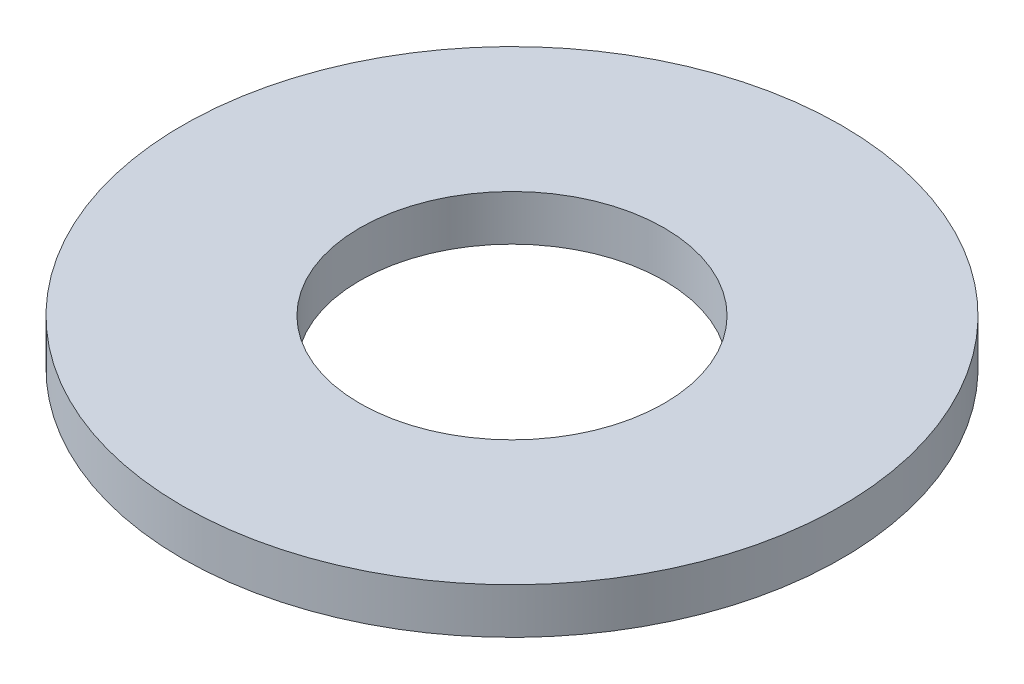
SolidWorks part; units mm, degrees
ref_plane "Front Plane" through (0, 0, 0) normal (0, 0, 1) x (1, 0, 0)
ref_plane "Top Plane" through (0, 0, 0) normal (0, 1, 0) x (1, 0, 0)
ref_plane "Right Plane" through (0, 0, 0) normal (1, 0, 0) x (0, 0, -1)
sketch "Sketch1" plane through (0, 0, 0) normal (0, 1, 0) x (1, 0, 0)
  circle A0 centre (0, 0) radius 65
  dimension "FLANGE_OD" = 130
extrude "Boss-Extrude1" add sketch "Sketch1" along normal blind 9
sketch "Sketch2" plane through (0, 0, 0) normal (0, 1, 0) x (1, 0, 0)
  circle A0 centre (0, 0) radius 30
  dimension "BORE_D" = 60
extrude "Cut-Extrude1" cut sketch "Sketch2" along normal through all
sketch "Sketch3" plane through (0, 9, 0) normal (0, 1, 0) x (1, 0, 0)
  circle A0 centre (0, 0) radius 22.3577 construction
  circle A1 centre (-22.3577, 0) radius 3.6229
  dimension "BOLT_D" = 7.2457
  dimension "BOLT_PCD" = 44.7154
extrude "Cut-Extrude2" cut sketch "Sketch3" against normal blind 5.8386 rebuild error yes
pattern_circular "CirPattern1" count 8 over 360 rebuild error yes
